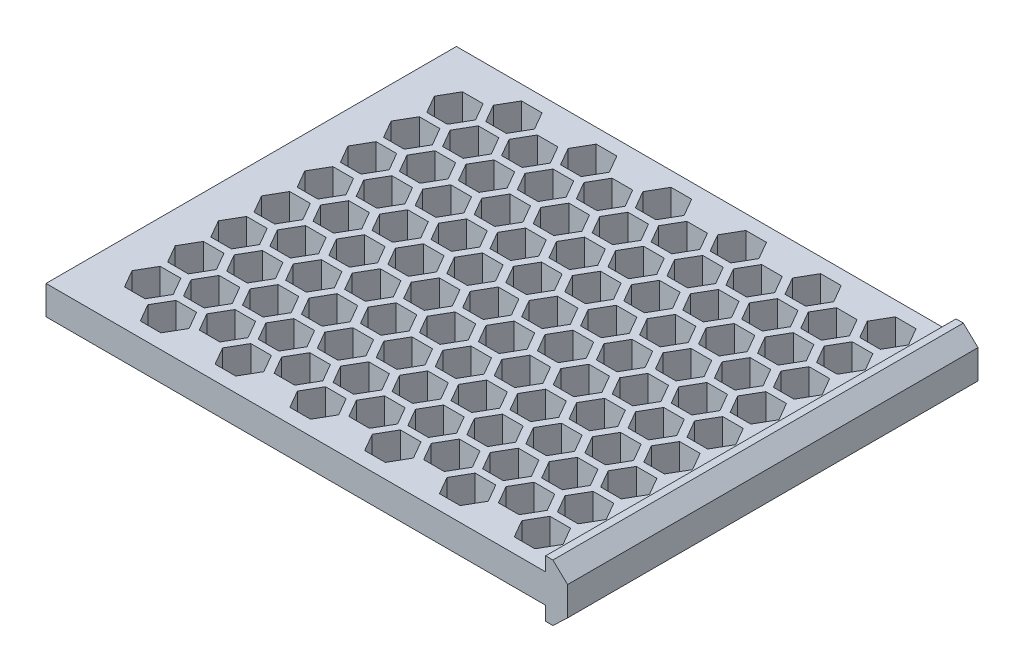
SolidWorks part; units mm, degrees
ref_plane "Front Plane" through (0, 0, 0) normal (0, 0, 1) x (1, 0, 0)
ref_plane "Top Plane" through (0, 0, 0) normal (0, 1, 0) x (1, 0, 0)
ref_plane "Right Plane" through (0, 0, 0) normal (1, 0, 0) x (0, 0, -1)
sketch "Sketch1" plane through (0, 0, 0) normal (0, 0, 1) x (1, 0, 0)
  line L0 (0, 4.05) -> (-140, 4.05)
  line L1 (0, -4.05) -> (-140, -4.05)
  line L2 (-140, -4.05) -> (-140, 4.05)
  line B0 (0, 7.95) -> (2.04, 7.95)
  line B1 (6.1524, 4.048) -> (6.1524, -4.048)
  line B2 (2.04, -7.95) -> (0, -7.95)
  line B3 (0, -7.95) -> (0, 7.95)
  line B4 (2.04, 7.95) -> (6.1524, 4.048)
  line B5 (6.1524, -4.048) -> (2.04, -7.95)
  line B6 (0, 4.05) -> (0, -4.05) construction
  dimension "D1" = 140
sketch_block_instance "Extrusion Profile-2"
sketch_block "Extrusion Profile" parameters "D1"=8.44, "D2"=2.6, "D3"=6, "D4"=16.7, "D6"=5.6686, "D7"=2.0404, "D8"=8.0963, "D9"=15.9, "D5"=2.4157
extrude "Boss-Extrude1" add sketch "Sketch1" along normal blind 115 contours L1 B3 L0 L2 | B2 B5 B1 B4 B0 B3 region at (-70, 0, 0) region at (2.7416, 0, 0)
sketch "Sketch2" plane through (0, 4.05, 0) normal (0, 1, 0) x (1, 0, 0)
  line L0 (-16.1488, -12.65) -> (-14.3301, -11.6) construction
  line L1 (-4.2265, -9.1) -> (-7.1132, -4.1)
  line L2 (-7.1132, -4.1) -> (-12.8868, -4.1)
  line L3 (-12.8868, -4.1) -> (-15.7735, -9.1)
  line L4 (-15.7735, -9.1) -> (-12.8868, -14.1)
  line L5 (-12.8868, -14.1) -> (-7.1132, -14.1)
  line L6 (-7.1132, -14.1) -> (-4.2265, -9.1)
  line L7 (0, -115) -> (0, 0) construction
  line L8 (-4.2265, -21.2) -> (-7.1132, -16.2)
  line L9 (-7.1132, -16.2) -> (-12.8868, -16.2)
  line L10 (-12.8868, -16.2) -> (-15.7735, -21.2)
  line L11 (-15.7735, -21.2) -> (-12.8868, -26.2)
  line L12 (-12.8868, -26.2) -> (-7.1132, -26.2)
  line L13 (-7.1132, -26.2) -> (-4.2265, -21.2)
  line L14 (-4.2265, -33.3) -> (-7.1132, -28.3)
  line L15 (-7.1132, -28.3) -> (-12.8868, -28.3)
  line L16 (-12.8868, -28.3) -> (-15.7735, -33.3)
  line L17 (-15.7735, -33.3) -> (-12.8868, -38.3)
  line L18 (-12.8868, -38.3) -> (-7.1132, -38.3)
  line L19 (-7.1132, -38.3) -> (-4.2265, -33.3)
  line L20 (-4.2265, -45.4) -> (-7.1132, -40.4)
  line L21 (-7.1132, -40.4) -> (-12.8868, -40.4)
  line L22 (-12.8868, -40.4) -> (-15.7735, -45.4)
  line L23 (-15.7735, -45.4) -> (-12.8868, -50.4)
  line L24 (-12.8868, -50.4) -> (-7.1132, -50.4)
  line L25 (-7.1132, -50.4) -> (-4.2265, -45.4)
  line L26 (-4.2265, -57.5) -> (-7.1132, -52.5)
  line L27 (-7.1132, -52.5) -> (-12.8868, -52.5)
  line L28 (-12.8868, -52.5) -> (-15.7735, -57.5)
  line L29 (-15.7735, -57.5) -> (-12.8868, -62.5)
  line L30 (-12.8868, -62.5) -> (-7.1132, -62.5)
  line L31 (-7.1132, -62.5) -> (-4.2265, -57.5)
  line L32 (-4.2265, -69.6) -> (-7.1132, -64.6)
  line L33 (-7.1132, -64.6) -> (-12.8868, -64.6)
  line L34 (-12.8868, -64.6) -> (-15.7735, -69.6)
  line L35 (-15.7735, -69.6) -> (-12.8868, -74.6)
  line L36 (-12.8868, -74.6) -> (-7.1132, -74.6)
  line L37 (-7.1132, -74.6) -> (-4.2265, -69.6)
  line L38 (-4.2265, -81.7) -> (-7.1132, -76.7)
  line L39 (-7.1132, -76.7) -> (-12.8868, -76.7)
  line L40 (-12.8868, -76.7) -> (-15.7735, -81.7)
  line L41 (-15.7735, -81.7) -> (-12.8868, -86.7)
  line L42 (-12.8868, -86.7) -> (-7.1132, -86.7)
  line L43 (-7.1132, -86.7) -> (-4.2265, -81.7)
  line L44 (-4.2265, -93.8) -> (-7.1132, -88.8)
  line L45 (-7.1132, -88.8) -> (-12.8868, -88.8)
  line L46 (-12.8868, -88.8) -> (-15.7735, -93.8)
  line L47 (-15.7735, -93.8) -> (-12.8868, -98.8)
  line L48 (-12.8868, -98.8) -> (-7.1132, -98.8)
  line L49 (-7.1132, -98.8) -> (-4.2265, -93.8)
  line L50 (-4.2265, -105.9) -> (-7.1132, -100.9)
  line L51 (-7.1132, -100.9) -> (-12.8868, -100.9)
  line L52 (-12.8868, -100.9) -> (-15.7735, -105.9)
  line L53 (-15.7735, -105.9) -> (-12.8868, -110.9)
  line L54 (-12.8868, -110.9) -> (-7.1132, -110.9)
  line L55 (-7.1132, -110.9) -> (-4.2265, -105.9)
  line L56 (-14.7054, -15.15) -> (-17.5922, -10.15)
  line L57 (-17.5922, -10.15) -> (-23.3657, -10.15)
  line L58 (-23.3657, -10.15) -> (-26.2524, -15.15)
  line L59 (-10, -4.1) -> (-10, 0) construction
  line L60 (0, 0) -> (-140, 0) construction
  line L61 (-10, -110.9) -> (-10, -115) construction
  line L62 (-26.2524, -15.15) -> (-23.3657, -20.15)
  line L69 (-4.2265, -118) -> (-7.1132, -113) [skipped]
  line L70 (-7.1132, -113) -> (-12.8868, -113) [skipped]
  line L71 (-12.8868, -113) -> (-15.7735, -118) [skipped]
  line L72 (-15.7735, -118) -> (-12.8868, -123) [skipped]
  line L73 (-12.8868, -123) -> (-7.1132, -123) [skipped]
  line L74 (-7.1132, -123) -> (-4.2265, -118) [skipped]
  line L75 (0, -115) -> (-140, -115) construction
  line L76 (-23.3657, -20.15) -> (-17.5922, -20.15)
  line L77 (-17.5922, -20.15) -> (-14.7054, -15.15)
  line L79 (-16.1488, -17.65) -> (-14.3301, -18.7) construction
  line L81 (-10, -14.1) -> (-10, -16.2) construction
  line L83 (-14.7054, -27.25) -> (-17.5922, -22.25)
  line L84 (-17.5922, -22.25) -> (-23.3657, -22.25)
  line L85 (-23.3657, -22.25) -> (-26.2524, -27.25)
  line L86 (-26.2524, -27.25) -> (-23.3657, -32.25)
  line L87 (-23.3657, -32.25) -> (-17.5922, -32.25)
  line L88 (-17.5922, -32.25) -> (-14.7054, -27.25)
  line L89 (-14.7054, -39.35) -> (-17.5922, -34.35)
  line L90 (-17.5922, -34.35) -> (-23.3657, -34.35)
  line L91 (-23.3657, -34.35) -> (-26.2524, -39.35)
  line L92 (-26.2524, -39.35) -> (-23.3657, -44.35)
  line L93 (-23.3657, -44.35) -> (-17.5922, -44.35)
  line L94 (-17.5922, -44.35) -> (-14.7054, -39.35)
  line L95 (-14.7054, -51.45) -> (-17.5922, -46.45)
  line L96 (-17.5922, -46.45) -> (-23.3657, -46.45)
  line L97 (-23.3657, -46.45) -> (-26.2524, -51.45)
  line L98 (-26.2524, -51.45) -> (-23.3657, -56.45)
  line L99 (-23.3657, -56.45) -> (-17.5922, -56.45)
  line L100 (-17.5922, -56.45) -> (-14.7054, -51.45)
  line L101 (-14.7054, -63.55) -> (-17.5922, -58.55)
  line L102 (-17.5922, -58.55) -> (-23.3657, -58.55)
  line L103 (-23.3657, -58.55) -> (-26.2524, -63.55)
  line L104 (-26.2524, -63.55) -> (-23.3657, -68.55)
  line L105 (-23.3657, -68.55) -> (-17.5922, -68.55)
  line L106 (-17.5922, -68.55) -> (-14.7054, -63.55)
  line L107 (-14.7054, -75.65) -> (-17.5922, -70.65)
  line L108 (-17.5922, -70.65) -> (-23.3657, -70.65)
  line L109 (-23.3657, -70.65) -> (-26.2524, -75.65)
  line L110 (-26.2524, -75.65) -> (-23.3657, -80.65)
  line L111 (-23.3657, -80.65) -> (-17.5922, -80.65)
  line L112 (-17.5922, -80.65) -> (-14.7054, -75.65)
  line L113 (-14.7054, -87.75) -> (-17.5922, -82.75)
  line L114 (-17.5922, -82.75) -> (-23.3657, -82.75)
  line L115 (-23.3657, -82.75) -> (-26.2524, -87.75)
  line L116 (-26.2524, -87.75) -> (-23.3657, -92.75)
  line L117 (-23.3657, -92.75) -> (-17.5922, -92.75)
  line L118 (-17.5922, -92.75) -> (-14.7054, -87.75)
  line L119 (-14.7054, -99.85) -> (-17.5922, -94.85)
  line L120 (-17.5922, -94.85) -> (-23.3657, -94.85)
  line L121 (-23.3657, -94.85) -> (-26.2524, -99.85)
  line L122 (-26.2524, -99.85) -> (-23.3657, -104.85)
  line L123 (-23.3657, -104.85) -> (-17.5922, -104.85)
  line L124 (-17.5922, -104.85) -> (-14.7054, -99.85)
  line L125 (-14.7054, -15.15) -> (-14.7054, -27.25) construction
  line L126 (-25.1843, -9.1) -> (-28.0711, -4.1)
  line L127 (-28.0711, -4.1) -> (-33.8446, -4.1)
  line L128 (-33.8446, -4.1) -> (-36.7313, -9.1)
  line L129 (-36.7313, -9.1) -> (-33.8446, -14.1)
  line L130 (-33.8446, -14.1) -> (-28.0711, -14.1)
  line L131 (-28.0711, -14.1) -> (-25.1843, -9.1)
  line L132 (-25.1843, -21.2) -> (-28.0711, -16.2)
  line L133 (-28.0711, -16.2) -> (-33.8446, -16.2)
  line L134 (-33.8446, -16.2) -> (-36.7313, -21.2)
  line L135 (-36.7313, -21.2) -> (-33.8446, -26.2)
  line L136 (-33.8446, -26.2) -> (-28.0711, -26.2)
  line L137 (-28.0711, -26.2) -> (-25.1843, -21.2)
  line L138 (-25.1843, -33.3) -> (-28.0711, -28.3)
  line L139 (-28.0711, -28.3) -> (-33.8446, -28.3)
  line L140 (-33.8446, -28.3) -> (-36.7313, -33.3)
  line L141 (-36.7313, -33.3) -> (-33.8446, -38.3)
  line L142 (-33.8446, -38.3) -> (-28.0711, -38.3)
  line L143 (-28.0711, -38.3) -> (-25.1843, -33.3)
  line L144 (-25.1843, -45.4) -> (-28.0711, -40.4)
  line L145 (-28.0711, -40.4) -> (-33.8446, -40.4)
  line L146 (-33.8446, -40.4) -> (-36.7313, -45.4)
  line L147 (-36.7313, -45.4) -> (-33.8446, -50.4)
  line L148 (-33.8446, -50.4) -> (-28.0711, -50.4)
  line L149 (-28.0711, -50.4) -> (-25.1843, -45.4)
  line L150 (-25.1843, -57.5) -> (-28.0711, -52.5)
  line L151 (-28.0711, -52.5) -> (-33.8446, -52.5)
  line L152 (-33.8446, -52.5) -> (-36.7313, -57.5)
  line L153 (-36.7313, -57.5) -> (-33.8446, -62.5)
  line L154 (-33.8446, -62.5) -> (-28.0711, -62.5)
  line L155 (-28.0711, -62.5) -> (-25.1843, -57.5)
  line L156 (-25.1843, -69.6) -> (-28.0711, -64.6)
  line L157 (-28.0711, -64.6) -> (-33.8446, -64.6)
  line L158 (-33.8446, -64.6) -> (-36.7313, -69.6)
  line L159 (-36.7313, -69.6) -> (-33.8446, -74.6)
  line L160 (-33.8446, -74.6) -> (-28.0711, -74.6)
  line L161 (-28.0711, -74.6) -> (-25.1843, -69.6)
  line L162 (-25.1843, -81.7) -> (-28.0711, -76.7)
  line L163 (-28.0711, -76.7) -> (-33.8446, -76.7)
  line L164 (-33.8446, -76.7) -> (-36.7313, -81.7)
  line L165 (-36.7313, -81.7) -> (-33.8446, -86.7)
  line L166 (-33.8446, -86.7) -> (-28.0711, -86.7)
  line L167 (-28.0711, -86.7) -> (-25.1843, -81.7)
  line L168 (-25.1843, -93.8) -> (-28.0711, -88.8)
  line L169 (-28.0711, -88.8) -> (-33.8446, -88.8)
  line L170 (-33.8446, -88.8) -> (-36.7313, -93.8)
  line L171 (-36.7313, -93.8) -> (-33.8446, -98.8)
  line L172 (-33.8446, -98.8) -> (-28.0711, -98.8)
  line L173 (-28.0711, -98.8) -> (-25.1843, -93.8)
  line L174 (-25.1843, -105.9) -> (-28.0711, -100.9)
  line L175 (-28.0711, -100.9) -> (-33.8446, -100.9)
  line L176 (-33.8446, -100.9) -> (-36.7313, -105.9)
  line L177 (-36.7313, -105.9) -> (-33.8446, -110.9)
  line L178 (-33.8446, -110.9) -> (-28.0711, -110.9)
  line L179 (-28.0711, -110.9) -> (-25.1843, -105.9)
  line L180 (-35.6632, -15.15) -> (-38.55, -10.15)
  line L181 (-38.55, -10.15) -> (-44.3235, -10.15)
  line L182 (-44.3235, -10.15) -> (-47.2102, -15.15)
  line L183 (-47.2102, -15.15) -> (-44.3235, -20.15)
  line L184 (-44.3235, -20.15) -> (-38.55, -20.15)
  line L185 (-38.55, -20.15) -> (-35.6632, -15.15)
  line L186 (-35.6632, -27.25) -> (-38.55, -22.25)
  line L187 (-38.55, -22.25) -> (-44.3235, -22.25)
  line L188 (-44.3235, -22.25) -> (-47.2102, -27.25)
  line L189 (-47.2102, -27.25) -> (-44.3235, -32.25)
  line L190 (-44.3235, -32.25) -> (-38.55, -32.25)
  line L191 (-38.55, -32.25) -> (-35.6632, -27.25)
  line L192 (-35.6632, -39.35) -> (-38.55, -34.35)
  line L193 (-38.55, -34.35) -> (-44.3235, -34.35)
  line L194 (-44.3235, -34.35) -> (-47.2102, -39.35)
  line L195 (-47.2102, -39.35) -> (-44.3235, -44.35)
  line L196 (-44.3235, -44.35) -> (-38.55, -44.35)
  line L197 (-38.55, -44.35) -> (-35.6632, -39.35)
  line L198 (-35.6632, -51.45) -> (-38.55, -46.45)
  line L199 (-38.55, -46.45) -> (-44.3235, -46.45)
  line L200 (-44.3235, -46.45) -> (-47.2102, -51.45)
  line L201 (-47.2102, -51.45) -> (-44.3235, -56.45)
  line L202 (-44.3235, -56.45) -> (-38.55, -56.45)
  line L203 (-38.55, -56.45) -> (-35.6632, -51.45)
  line L204 (-35.6632, -63.55) -> (-38.55, -58.55)
  line L205 (-38.55, -58.55) -> (-44.3235, -58.55)
  line L206 (-44.3235, -58.55) -> (-47.2102, -63.55)
  line L207 (-47.2102, -63.55) -> (-44.3235, -68.55)
  line L208 (-44.3235, -68.55) -> (-38.55, -68.55)
  line L209 (-38.55, -68.55) -> (-35.6632, -63.55)
  line L210 (-35.6632, -75.65) -> (-38.55, -70.65)
  line L211 (-38.55, -70.65) -> (-44.3235, -70.65)
  line L212 (-44.3235, -70.65) -> (-47.2102, -75.65)
  line L213 (-47.2102, -75.65) -> (-44.3235, -80.65)
  line L214 (-44.3235, -80.65) -> (-38.55, -80.65)
  line L215 (-38.55, -80.65) -> (-35.6632, -75.65)
  line L216 (-35.6632, -87.75) -> (-38.55, -82.75)
  line L217 (-38.55, -82.75) -> (-44.3235, -82.75)
  line L218 (-44.3235, -82.75) -> (-47.2102, -87.75)
  line L219 (-47.2102, -87.75) -> (-44.3235, -92.75)
  line L220 (-44.3235, -92.75) -> (-38.55, -92.75)
  line L221 (-38.55, -92.75) -> (-35.6632, -87.75)
  line L222 (-35.6632, -99.85) -> (-38.55, -94.85)
  line L223 (-38.55, -94.85) -> (-44.3235, -94.85)
  line L224 (-44.3235, -94.85) -> (-47.2102, -99.85)
  line L225 (-47.2102, -99.85) -> (-44.3235, -104.85)
  line L226 (-44.3235, -104.85) -> (-38.55, -104.85)
  line L227 (-38.55, -104.85) -> (-35.6632, -99.85)
  line L228 (-37.1066, -12.65) -> (-35.2879, -11.6) construction
  line L229 (-30.9578, -4.1) -> (-30.9578, 0) construction
  line L230 (-30.9578, -110.9) -> (-30.9578, -115) construction
  line L231 (-37.1066, -17.65) -> (-35.2879, -18.7) construction
  line L232 (-30.9578, -15.15) -> (-30.9578, -14.1)
  line L233 (-35.6632, -15.15) -> (-35.6632, -27.25) construction
  line L234 (-46.1421, -9.1) -> (-49.0289, -4.1)
  line L235 (-49.0289, -4.1) -> (-54.8024, -4.1)
  line L236 (-54.8024, -4.1) -> (-57.6891, -9.1)
  line L237 (-57.6891, -9.1) -> (-54.8024, -14.1)
  line L238 (-54.8024, -14.1) -> (-49.0289, -14.1)
  line L239 (-49.0289, -14.1) -> (-46.1421, -9.1)
  line L240 (-46.1421, -21.2) -> (-49.0289, -16.2)
  line L241 (-49.0289, -16.2) -> (-54.8024, -16.2)
  line L242 (-54.8024, -16.2) -> (-57.6891, -21.2)
  line L243 (-57.6891, -21.2) -> (-54.8024, -26.2)
  line L244 (-54.8024, -26.2) -> (-49.0289, -26.2)
  line L245 (-49.0289, -26.2) -> (-46.1421, -21.2)
  line L246 (-46.1421, -33.3) -> (-49.0289, -28.3)
  line L247 (-49.0289, -28.3) -> (-54.8024, -28.3)
  line L248 (-54.8024, -28.3) -> (-57.6891, -33.3)
  line L249 (-57.6891, -33.3) -> (-54.8024, -38.3)
  line L250 (-54.8024, -38.3) -> (-49.0289, -38.3)
  line L251 (-49.0289, -38.3) -> (-46.1421, -33.3)
  line L252 (-46.1421, -45.4) -> (-49.0289, -40.4)
  line L253 (-49.0289, -40.4) -> (-54.8024, -40.4)
  line L254 (-54.8024, -40.4) -> (-57.6891, -45.4)
  line L255 (-57.6891, -45.4) -> (-54.8024, -50.4)
  line L256 (-54.8024, -50.4) -> (-49.0289, -50.4)
  line L257 (-49.0289, -50.4) -> (-46.1421, -45.4)
  line L258 (-46.1421, -57.5) -> (-49.0289, -52.5)
  line L259 (-49.0289, -52.5) -> (-54.8024, -52.5)
  line L260 (-54.8024, -52.5) -> (-57.6891, -57.5)
  line L261 (-57.6891, -57.5) -> (-54.8024, -62.5)
  line L262 (-54.8024, -62.5) -> (-49.0289, -62.5)
  line L263 (-49.0289, -62.5) -> (-46.1421, -57.5)
  line L264 (-46.1421, -69.6) -> (-49.0289, -64.6)
  line L265 (-49.0289, -64.6) -> (-54.8024, -64.6)
  line L266 (-54.8024, -64.6) -> (-57.6891, -69.6)
  line L267 (-57.6891, -69.6) -> (-54.8024, -74.6)
  line L268 (-54.8024, -74.6) -> (-49.0289, -74.6)
  line L269 (-49.0289, -74.6) -> (-46.1421, -69.6)
  line L270 (-46.1421, -81.7) -> (-49.0289, -76.7)
  line L271 (-49.0289, -76.7) -> (-54.8024, -76.7)
  line L272 (-54.8024, -76.7) -> (-57.6891, -81.7)
  line L273 (-57.6891, -81.7) -> (-54.8024, -86.7)
  line L274 (-54.8024, -86.7) -> (-49.0289, -86.7)
  line L275 (-49.0289, -86.7) -> (-46.1421, -81.7)
  line L276 (-46.1421, -93.8) -> (-49.0289, -88.8)
  line L277 (-49.0289, -88.8) -> (-54.8024, -88.8)
  line L278 (-54.8024, -88.8) -> (-57.6891, -93.8)
  line L279 (-57.6891, -93.8) -> (-54.8024, -98.8)
  line L280 (-54.8024, -98.8) -> (-49.0289, -98.8)
  line L281 (-49.0289, -98.8) -> (-46.1421, -93.8)
  line L282 (-46.1421, -105.9) -> (-49.0289, -100.9)
  line L283 (-49.0289, -100.9) -> (-54.8024, -100.9)
  line L284 (-54.8024, -100.9) -> (-57.6891, -105.9)
  line L285 (-57.6891, -105.9) -> (-54.8024, -110.9)
  line L286 (-54.8024, -110.9) -> (-49.0289, -110.9)
  line L287 (-49.0289, -110.9) -> (-46.1421, -105.9)
  line L288 (-56.621, -15.15) -> (-59.5078, -10.15)
  line L289 (-59.5078, -10.15) -> (-65.2813, -10.15)
  line L290 (-65.2813, -10.15) -> (-68.168, -15.15)
  line L291 (-68.168, -15.15) -> (-65.2813, -20.15)
  line L292 (-65.2813, -20.15) -> (-59.5078, -20.15)
  line L293 (-59.5078, -20.15) -> (-56.621, -15.15)
  line L294 (-56.621, -27.25) -> (-59.5078, -22.25)
  line L295 (-59.5078, -22.25) -> (-65.2813, -22.25)
  line L296 (-65.2813, -22.25) -> (-68.168, -27.25)
  line L297 (-68.168, -27.25) -> (-65.2813, -32.25)
  line L298 (-65.2813, -32.25) -> (-59.5078, -32.25)
  line L299 (-59.5078, -32.25) -> (-56.621, -27.25)
  line L300 (-56.621, -39.35) -> (-59.5078, -34.35)
  line L301 (-59.5078, -34.35) -> (-65.2813, -34.35)
  line L302 (-65.2813, -34.35) -> (-68.168, -39.35)
  line L303 (-68.168, -39.35) -> (-65.2813, -44.35)
  line L304 (-65.2813, -44.35) -> (-59.5078, -44.35)
  line L305 (-59.5078, -44.35) -> (-56.621, -39.35)
  line L306 (-56.621, -51.45) -> (-59.5078, -46.45)
  line L307 (-59.5078, -46.45) -> (-65.2813, -46.45)
  line L308 (-65.2813, -46.45) -> (-68.168, -51.45)
  line L309 (-68.168, -51.45) -> (-65.2813, -56.45)
  line L310 (-65.2813, -56.45) -> (-59.5078, -56.45)
  line L311 (-59.5078, -56.45) -> (-56.621, -51.45)
  line L312 (-56.621, -63.55) -> (-59.5078, -58.55)
  line L313 (-59.5078, -58.55) -> (-65.2813, -58.55)
  line L314 (-65.2813, -58.55) -> (-68.168, -63.55)
  line L315 (-68.168, -63.55) -> (-65.2813, -68.55)
  line L316 (-65.2813, -68.55) -> (-59.5078, -68.55)
  line L317 (-59.5078, -68.55) -> (-56.621, -63.55)
  line L318 (-56.621, -75.65) -> (-59.5078, -70.65)
  line L319 (-59.5078, -70.65) -> (-65.2813, -70.65)
  line L320 (-65.2813, -70.65) -> (-68.168, -75.65)
  line L321 (-68.168, -75.65) -> (-65.2813, -80.65)
  line L322 (-65.2813, -80.65) -> (-59.5078, -80.65)
  line L323 (-59.5078, -80.65) -> (-56.621, -75.65)
  line L324 (-56.621, -87.75) -> (-59.5078, -82.75)
  line L325 (-59.5078, -82.75) -> (-65.2813, -82.75)
  line L326 (-65.2813, -82.75) -> (-68.168, -87.75)
  line L327 (-68.168, -87.75) -> (-65.2813, -92.75)
  line L328 (-65.2813, -92.75) -> (-59.5078, -92.75)
  line L329 (-59.5078, -92.75) -> (-56.621, -87.75)
  line L330 (-56.621, -99.85) -> (-59.5078, -94.85)
  line L331 (-59.5078, -94.85) -> (-65.2813, -94.85)
  line L332 (-65.2813, -94.85) -> (-68.168, -99.85)
  line L333 (-68.168, -99.85) -> (-65.2813, -104.85)
  line L334 (-65.2813, -104.85) -> (-59.5078, -104.85)
  line L335 (-59.5078, -104.85) -> (-56.621, -99.85)
  line L336 (-58.0644, -12.65) -> (-56.2458, -11.6) construction
  line L337 (-51.9156, -4.1) -> (-51.9156, 0) construction
  line L338 (-51.9156, -110.9) -> (-51.9156, -115) construction
  line L339 (-58.0644, -17.65) -> (-56.2458, -18.7) construction
  line L340 (-51.9156, -14.1) -> (-51.9156, -16.2) construction
  line L341 (-56.621, -15.15) -> (-56.621, -27.25) construction
  line L342 (-67.0999, -9.1) -> (-69.9867, -4.1)
  line L343 (-69.9867, -4.1) -> (-75.7602, -4.1)
  line L344 (-75.7602, -4.1) -> (-78.6469, -9.1)
  line L345 (-78.6469, -9.1) -> (-75.7602, -14.1)
  line L346 (-75.7602, -14.1) -> (-69.9867, -14.1)
  line L347 (-69.9867, -14.1) -> (-67.0999, -9.1)
  line L348 (-67.0999, -21.2) -> (-69.9867, -16.2)
  line L349 (-69.9867, -16.2) -> (-75.7602, -16.2)
  line L350 (-75.7602, -16.2) -> (-78.6469, -21.2)
  line L351 (-78.6469, -21.2) -> (-75.7602, -26.2)
  line L352 (-75.7602, -26.2) -> (-69.9867, -26.2)
  line L353 (-69.9867, -26.2) -> (-67.0999, -21.2)
  line L354 (-67.0999, -33.3) -> (-69.9867, -28.3)
  line L355 (-69.9867, -28.3) -> (-75.7602, -28.3)
  line L356 (-75.7602, -28.3) -> (-78.6469, -33.3)
  line L357 (-78.6469, -33.3) -> (-75.7602, -38.3)
  line L358 (-75.7602, -38.3) -> (-69.9867, -38.3)
  line L359 (-69.9867, -38.3) -> (-67.0999, -33.3)
  line L360 (-67.0999, -45.4) -> (-69.9867, -40.4)
  line L361 (-69.9867, -40.4) -> (-75.7602, -40.4)
  line L362 (-75.7602, -40.4) -> (-78.6469, -45.4)
  line L363 (-78.6469, -45.4) -> (-75.7602, -50.4)
  line L364 (-75.7602, -50.4) -> (-69.9867, -50.4)
  line L365 (-69.9867, -50.4) -> (-67.0999, -45.4)
  line L366 (-67.0999, -57.5) -> (-69.9867, -52.5)
  line L367 (-69.9867, -52.5) -> (-75.7602, -52.5)
  line L368 (-75.7602, -52.5) -> (-78.6469, -57.5)
  line L369 (-78.6469, -57.5) -> (-75.7602, -62.5)
  line L370 (-75.7602, -62.5) -> (-69.9867, -62.5)
  line L371 (-69.9867, -62.5) -> (-67.0999, -57.5)
  line L372 (-67.0999, -69.6) -> (-69.9867, -64.6)
  line L373 (-69.9867, -64.6) -> (-75.7602, -64.6)
  line L374 (-75.7602, -64.6) -> (-78.6469, -69.6)
  line L375 (-78.6469, -69.6) -> (-75.7602, -74.6)
  line L376 (-75.7602, -74.6) -> (-69.9867, -74.6)
  line L377 (-69.9867, -74.6) -> (-67.0999, -69.6)
  line L378 (-67.0999, -81.7) -> (-69.9867, -76.7)
  line L379 (-69.9867, -76.7) -> (-75.7602, -76.7)
  line L380 (-75.7602, -76.7) -> (-78.6469, -81.7)
  line L381 (-78.6469, -81.7) -> (-75.7602, -86.7)
  line L382 (-75.7602, -86.7) -> (-69.9867, -86.7)
  line L383 (-69.9867, -86.7) -> (-67.0999, -81.7)
  line L384 (-67.0999, -93.8) -> (-69.9867, -88.8)
  line L385 (-69.9867, -88.8) -> (-75.7602, -88.8)
  line L386 (-75.7602, -88.8) -> (-78.6469, -93.8)
  line L387 (-78.6469, -93.8) -> (-75.7602, -98.8)
  line L388 (-75.7602, -98.8) -> (-69.9867, -98.8)
  line L389 (-69.9867, -98.8) -> (-67.0999, -93.8)
  line L390 (-67.0999, -105.9) -> (-69.9867, -100.9)
  line L391 (-69.9867, -100.9) -> (-75.7602, -100.9)
  line L392 (-75.7602, -100.9) -> (-78.6469, -105.9)
  line L393 (-78.6469, -105.9) -> (-75.7602, -110.9)
  line L394 (-75.7602, -110.9) -> (-69.9867, -110.9)
  line L395 (-69.9867, -110.9) -> (-67.0999, -105.9)
  line L396 (-77.5788, -15.15) -> (-80.4656, -10.15)
  line L397 (-80.4656, -10.15) -> (-86.2391, -10.15)
  line L398 (-86.2391, -10.15) -> (-89.1259, -15.15)
  line L399 (-89.1259, -15.15) -> (-86.2391, -20.15)
  line L400 (-86.2391, -20.15) -> (-80.4656, -20.15)
  line L401 (-80.4656, -20.15) -> (-77.5788, -15.15)
  line L402 (-77.5788, -27.25) -> (-80.4656, -22.25)
  line L403 (-80.4656, -22.25) -> (-86.2391, -22.25)
  line L404 (-86.2391, -22.25) -> (-89.1259, -27.25)
  line L405 (-89.1259, -27.25) -> (-86.2391, -32.25)
  line L406 (-86.2391, -32.25) -> (-80.4656, -32.25)
  line L407 (-80.4656, -32.25) -> (-77.5788, -27.25)
  line L408 (-77.5788, -39.35) -> (-80.4656, -34.35)
  line L409 (-80.4656, -34.35) -> (-86.2391, -34.35)
  line L410 (-86.2391, -34.35) -> (-89.1259, -39.35)
  line L411 (-89.1259, -39.35) -> (-86.2391, -44.35)
  line L412 (-86.2391, -44.35) -> (-80.4656, -44.35)
  line L413 (-80.4656, -44.35) -> (-77.5788, -39.35)
  line L414 (-77.5788, -51.45) -> (-80.4656, -46.45)
  line L415 (-80.4656, -46.45) -> (-86.2391, -46.45)
  line L416 (-86.2391, -46.45) -> (-89.1259, -51.45)
  line L417 (-89.1259, -51.45) -> (-86.2391, -56.45)
  line L418 (-86.2391, -56.45) -> (-80.4656, -56.45)
  line L419 (-80.4656, -56.45) -> (-77.5788, -51.45)
  line L420 (-77.5788, -63.55) -> (-80.4656, -58.55)
  line L421 (-80.4656, -58.55) -> (-86.2391, -58.55)
  line L422 (-86.2391, -58.55) -> (-89.1259, -63.55)
  line L423 (-89.1259, -63.55) -> (-86.2391, -68.55)
  line L424 (-86.2391, -68.55) -> (-80.4656, -68.55)
  line L425 (-80.4656, -68.55) -> (-77.5788, -63.55)
  line L426 (-77.5788, -75.65) -> (-80.4656, -70.65)
  line L427 (-80.4656, -70.65) -> (-86.2391, -70.65)
  line L428 (-86.2391, -70.65) -> (-89.1259, -75.65)
  line L429 (-89.1259, -75.65) -> (-86.2391, -80.65)
  line L430 (-86.2391, -80.65) -> (-80.4656, -80.65)
  line L431 (-80.4656, -80.65) -> (-77.5788, -75.65)
  line L432 (-77.5788, -87.75) -> (-80.4656, -82.75)
  line L433 (-80.4656, -82.75) -> (-86.2391, -82.75)
  line L434 (-86.2391, -82.75) -> (-89.1259, -87.75)
  line L435 (-89.1259, -87.75) -> (-86.2391, -92.75)
  line L436 (-86.2391, -92.75) -> (-80.4656, -92.75)
  line L437 (-80.4656, -92.75) -> (-77.5788, -87.75)
  line L438 (-77.5788, -99.85) -> (-80.4656, -94.85)
  line L439 (-80.4656, -94.85) -> (-86.2391, -94.85)
  line L440 (-86.2391, -94.85) -> (-89.1259, -99.85)
  line L441 (-89.1259, -99.85) -> (-86.2391, -104.85)
  line L442 (-86.2391, -104.85) -> (-80.4656, -104.85)
  line L443 (-80.4656, -104.85) -> (-77.5788, -99.85)
  line L444 (-79.0222, -12.65) -> (-77.2036, -11.6) construction
  line L445 (-72.8734, -4.1) -> (-72.8734, 0) construction
  line L446 (-72.8734, -110.9) -> (-72.8734, -115) construction
  line L447 (-79.0222, -17.65) -> (-77.2036, -18.7) construction
  line L448 (-72.8734, -14.1) -> (-72.8734, -16.2) construction
  line L449 (-77.5788, -15.15) -> (-77.5788, -27.25) construction
  line L450 (-88.0578, -9.1) -> (-90.9445, -4.1)
  line L451 (-90.9445, -4.1) -> (-96.718, -4.1)
  line L452 (-96.718, -4.1) -> (-99.6048, -9.1)
  line L453 (-99.6048, -9.1) -> (-96.718, -14.1)
  line L454 (-96.718, -14.1) -> (-90.9445, -14.1)
  line L455 (-90.9445, -14.1) -> (-88.0578, -9.1)
  line L456 (-88.0578, -21.2) -> (-90.9445, -16.2)
  line L457 (-90.9445, -16.2) -> (-96.718, -16.2)
  line L458 (-96.718, -16.2) -> (-99.6048, -21.2)
  line L459 (-99.6048, -21.2) -> (-96.718, -26.2)
  line L460 (-96.718, -26.2) -> (-90.9445, -26.2)
  line L461 (-90.9445, -26.2) -> (-88.0578, -21.2)
  line L462 (-88.0578, -33.3) -> (-90.9445, -28.3)
  line L463 (-90.9445, -28.3) -> (-96.718, -28.3)
  line L464 (-96.718, -28.3) -> (-99.6048, -33.3)
  line L465 (-99.6048, -33.3) -> (-96.718, -38.3)
  line L466 (-96.718, -38.3) -> (-90.9445, -38.3)
  line L467 (-90.9445, -38.3) -> (-88.0578, -33.3)
  line L468 (-88.0578, -45.4) -> (-90.9445, -40.4)
  line L469 (-90.9445, -40.4) -> (-96.718, -40.4)
  line L470 (-96.718, -40.4) -> (-99.6048, -45.4)
  line L471 (-99.6048, -45.4) -> (-96.718, -50.4)
  line L472 (-96.718, -50.4) -> (-90.9445, -50.4)
  line L473 (-90.9445, -50.4) -> (-88.0578, -45.4)
  line L474 (-88.0578, -57.5) -> (-90.9445, -52.5)
  line L475 (-90.9445, -52.5) -> (-96.718, -52.5)
  line L476 (-96.718, -52.5) -> (-99.6048, -57.5)
  line L477 (-99.6048, -57.5) -> (-96.718, -62.5)
  line L478 (-96.718, -62.5) -> (-90.9445, -62.5)
  line L479 (-90.9445, -62.5) -> (-88.0578, -57.5)
  line L480 (-88.0578, -69.6) -> (-90.9445, -64.6)
  line L481 (-90.9445, -64.6) -> (-96.718, -64.6)
  line L482 (-96.718, -64.6) -> (-99.6048, -69.6)
  line L483 (-99.6048, -69.6) -> (-96.718, -74.6)
  line L484 (-96.718, -74.6) -> (-90.9445, -74.6)
  line L485 (-90.9445, -74.6) -> (-88.0578, -69.6)
  line L486 (-88.0578, -81.7) -> (-90.9445, -76.7)
  line L487 (-90.9445, -76.7) -> (-96.718, -76.7)
  line L488 (-96.718, -76.7) -> (-99.6048, -81.7)
  line L489 (-99.6048, -81.7) -> (-96.718, -86.7)
  line L490 (-96.718, -86.7) -> (-90.9445, -86.7)
  line L491 (-90.9445, -86.7) -> (-88.0578, -81.7)
  line L492 (-88.0578, -93.8) -> (-90.9445, -88.8)
  line L493 (-90.9445, -88.8) -> (-96.718, -88.8)
  line L494 (-96.718, -88.8) -> (-99.6048, -93.8)
  line L495 (-99.6048, -93.8) -> (-96.718, -98.8)
  line L496 (-96.718, -98.8) -> (-90.9445, -98.8)
  line L497 (-90.9445, -98.8) -> (-88.0578, -93.8)
  line L498 (-88.0578, -105.9) -> (-90.9445, -100.9)
  line L499 (-90.9445, -100.9) -> (-96.718, -100.9)
  line L500 (-96.718, -100.9) -> (-99.6048, -105.9)
  line L501 (-99.6048, -105.9) -> (-96.718, -110.9)
  line L502 (-96.718, -110.9) -> (-90.9445, -110.9)
  line L503 (-90.9445, -110.9) -> (-88.0578, -105.9)
  line L504 (-98.5367, -15.15) -> (-101.4234, -10.15)
  line L505 (-101.4234, -10.15) -> (-107.1969, -10.15)
  line L506 (-107.1969, -10.15) -> (-110.0837, -15.15)
  line L507 (-110.0837, -15.15) -> (-107.1969, -20.15)
  line L508 (-107.1969, -20.15) -> (-101.4234, -20.15)
  line L509 (-101.4234, -20.15) -> (-98.5367, -15.15)
  line L510 (-98.5367, -27.25) -> (-101.4234, -22.25)
  line L511 (-101.4234, -22.25) -> (-107.1969, -22.25)
  line L512 (-107.1969, -22.25) -> (-110.0837, -27.25)
  line L513 (-110.0837, -27.25) -> (-107.1969, -32.25)
  line L514 (-107.1969, -32.25) -> (-101.4234, -32.25)
  line L515 (-101.4234, -32.25) -> (-98.5367, -27.25)
  line L516 (-98.5367, -39.35) -> (-101.4234, -34.35)
  line L517 (-101.4234, -34.35) -> (-107.1969, -34.35)
  line L518 (-107.1969, -34.35) -> (-110.0837, -39.35)
  line L519 (-110.0837, -39.35) -> (-107.1969, -44.35)
  line L520 (-107.1969, -44.35) -> (-101.4234, -44.35)
  line L521 (-101.4234, -44.35) -> (-98.5367, -39.35)
  line L522 (-98.5367, -51.45) -> (-101.4234, -46.45)
  line L523 (-101.4234, -46.45) -> (-107.1969, -46.45)
  line L524 (-107.1969, -46.45) -> (-110.0837, -51.45)
  line L525 (-110.0837, -51.45) -> (-107.1969, -56.45)
  line L526 (-107.1969, -56.45) -> (-101.4234, -56.45)
  line L527 (-101.4234, -56.45) -> (-98.5367, -51.45)
  line L528 (-98.5367, -63.55) -> (-101.4234, -58.55)
  line L529 (-101.4234, -58.55) -> (-107.1969, -58.55)
  line L530 (-107.1969, -58.55) -> (-110.0837, -63.55)
  line L531 (-110.0837, -63.55) -> (-107.1969, -68.55)
  line L532 (-107.1969, -68.55) -> (-101.4234, -68.55)
  line L533 (-101.4234, -68.55) -> (-98.5367, -63.55)
  line L534 (-98.5367, -75.65) -> (-101.4234, -70.65)
  line L535 (-101.4234, -70.65) -> (-107.1969, -70.65)
  line L536 (-107.1969, -70.65) -> (-110.0837, -75.65)
  line L537 (-110.0837, -75.65) -> (-107.1969, -80.65)
  line L538 (-107.1969, -80.65) -> (-101.4234, -80.65)
  line L539 (-101.4234, -80.65) -> (-98.5367, -75.65)
  line L540 (-98.5367, -87.75) -> (-101.4234, -82.75)
  line L541 (-101.4234, -82.75) -> (-107.1969, -82.75)
  line L542 (-107.1969, -82.75) -> (-110.0837, -87.75)
  line L543 (-110.0837, -87.75) -> (-107.1969, -92.75)
  line L544 (-107.1969, -92.75) -> (-101.4234, -92.75)
  line L545 (-101.4234, -92.75) -> (-98.5367, -87.75)
  line L546 (-98.5367, -99.85) -> (-101.4234, -94.85)
  line L547 (-101.4234, -94.85) -> (-107.1969, -94.85)
  line L548 (-107.1969, -94.85) -> (-110.0837, -99.85)
  line L549 (-110.0837, -99.85) -> (-107.1969, -104.85)
  line L550 (-107.1969, -104.85) -> (-101.4234, -104.85)
  line L551 (-101.4234, -104.85) -> (-98.5367, -99.85)
  line L552 (-99.98, -12.65) -> (-98.1614, -11.6) construction
  line L553 (-93.8313, -4.1) -> (-93.8313, 0) construction
  line L554 (-93.8313, -110.9) -> (-93.8313, -115) construction
  line L555 (-99.98, -17.65) -> (-98.1614, -18.7) construction
  line L556 (-93.8313, -14.1) -> (-93.8313, -16.2) construction
  line L557 (-98.5367, -15.15) -> (-98.5367, -27.25) construction
  line L558 (-109.0156, -9.1) -> (-111.9023, -4.1)
  line L559 (-111.9023, -4.1) -> (-117.6758, -4.1)
  line L560 (-117.6758, -4.1) -> (-120.5626, -9.1)
  line L561 (-120.5626, -9.1) -> (-117.6758, -14.1)
  line L562 (-117.6758, -14.1) -> (-111.9023, -14.1)
  line L563 (-111.9023, -14.1) -> (-109.0156, -9.1)
  line L564 (-109.0156, -21.2) -> (-111.9023, -16.2)
  line L565 (-111.9023, -16.2) -> (-117.6758, -16.2)
  line L566 (-117.6758, -16.2) -> (-120.5626, -21.2)
  line L567 (-120.5626, -21.2) -> (-117.6758, -26.2)
  line L568 (-117.6758, -26.2) -> (-111.9023, -26.2)
  line L569 (-111.9023, -26.2) -> (-109.0156, -21.2)
  line L570 (-109.0156, -33.3) -> (-111.9023, -28.3)
  line L571 (-111.9023, -28.3) -> (-117.6758, -28.3)
  line L572 (-117.6758, -28.3) -> (-120.5626, -33.3)
  line L573 (-120.5626, -33.3) -> (-117.6758, -38.3)
  line L574 (-117.6758, -38.3) -> (-111.9023, -38.3)
  line L575 (-111.9023, -38.3) -> (-109.0156, -33.3)
  line L576 (-109.0156, -45.4) -> (-111.9023, -40.4)
  line L577 (-111.9023, -40.4) -> (-117.6758, -40.4)
  line L578 (-117.6758, -40.4) -> (-120.5626, -45.4)
  line L579 (-120.5626, -45.4) -> (-117.6758, -50.4)
  line L580 (-117.6758, -50.4) -> (-111.9023, -50.4)
  line L581 (-111.9023, -50.4) -> (-109.0156, -45.4)
  line L582 (-109.0156, -57.5) -> (-111.9023, -52.5)
  line L583 (-111.9023, -52.5) -> (-117.6758, -52.5)
  line L584 (-117.6758, -52.5) -> (-120.5626, -57.5)
  line L585 (-120.5626, -57.5) -> (-117.6758, -62.5)
  line L586 (-117.6758, -62.5) -> (-111.9023, -62.5)
  line L587 (-111.9023, -62.5) -> (-109.0156, -57.5)
  line L588 (-109.0156, -69.6) -> (-111.9023, -64.6)
  line L589 (-111.9023, -64.6) -> (-117.6758, -64.6)
  line L590 (-117.6758, -64.6) -> (-120.5626, -69.6)
  line L591 (-120.5626, -69.6) -> (-117.6758, -74.6)
  line L592 (-117.6758, -74.6) -> (-111.9023, -74.6)
  line L593 (-111.9023, -74.6) -> (-109.0156, -69.6)
  line L594 (-109.0156, -81.7) -> (-111.9023, -76.7)
  line L595 (-111.9023, -76.7) -> (-117.6758, -76.7)
  line L596 (-117.6758, -76.7) -> (-120.5626, -81.7)
  line L597 (-120.5626, -81.7) -> (-117.6758, -86.7)
  line L598 (-117.6758, -86.7) -> (-111.9023, -86.7)
  line L599 (-111.9023, -86.7) -> (-109.0156, -81.7)
  line L600 (-109.0156, -93.8) -> (-111.9023, -88.8)
  line L601 (-111.9023, -88.8) -> (-117.6758, -88.8)
  line L602 (-117.6758, -88.8) -> (-120.5626, -93.8)
  line L603 (-120.5626, -93.8) -> (-117.6758, -98.8)
  line L604 (-117.6758, -98.8) -> (-111.9023, -98.8)
  line L605 (-111.9023, -98.8) -> (-109.0156, -93.8)
  line L606 (-109.0156, -105.9) -> (-111.9023, -100.9)
  line L607 (-111.9023, -100.9) -> (-117.6758, -100.9)
  line L608 (-117.6758, -100.9) -> (-120.5626, -105.9)
  line L609 (-120.5626, -105.9) -> (-117.6758, -110.9)
  line L610 (-117.6758, -110.9) -> (-111.9023, -110.9)
  line L611 (-111.9023, -110.9) -> (-109.0156, -105.9)
  line L612 (-119.4945, -15.15) -> (-122.3812, -10.15)
  line L613 (-122.3812, -10.15) -> (-128.1547, -10.15)
  line L614 (-128.1547, -10.15) -> (-131.0415, -15.15)
  line L615 (-131.0415, -15.15) -> (-128.1547, -20.15)
  line L616 (-128.1547, -20.15) -> (-122.3812, -20.15)
  line L617 (-122.3812, -20.15) -> (-119.4945, -15.15)
  line L618 (-119.4945, -27.25) -> (-122.3812, -22.25)
  line L619 (-122.3812, -22.25) -> (-128.1547, -22.25)
  line L620 (-128.1547, -22.25) -> (-131.0415, -27.25)
  line L621 (-131.0415, -27.25) -> (-128.1547, -32.25)
  line L622 (-128.1547, -32.25) -> (-122.3812, -32.25)
  line L623 (-122.3812, -32.25) -> (-119.4945, -27.25)
  line L624 (-119.4945, -39.35) -> (-122.3812, -34.35)
  line L625 (-122.3812, -34.35) -> (-128.1547, -34.35)
  line L626 (-128.1547, -34.35) -> (-131.0415, -39.35)
  line L627 (-131.0415, -39.35) -> (-128.1547, -44.35)
  line L628 (-128.1547, -44.35) -> (-122.3812, -44.35)
  line L629 (-122.3812, -44.35) -> (-119.4945, -39.35)
  line L630 (-119.4945, -51.45) -> (-122.3812, -46.45)
  line L631 (-122.3812, -46.45) -> (-128.1547, -46.45)
  line L632 (-128.1547, -46.45) -> (-131.0415, -51.45)
  line L633 (-131.0415, -51.45) -> (-128.1547, -56.45)
  line L634 (-128.1547, -56.45) -> (-122.3812, -56.45)
  line L635 (-122.3812, -56.45) -> (-119.4945, -51.45)
  line L636 (-119.4945, -63.55) -> (-122.3812, -58.55)
  line L637 (-122.3812, -58.55) -> (-128.1547, -58.55)
  line L638 (-128.1547, -58.55) -> (-131.0415, -63.55)
  line L639 (-131.0415, -63.55) -> (-128.1547, -68.55)
  line L640 (-128.1547, -68.55) -> (-122.3812, -68.55)
  line L641 (-122.3812, -68.55) -> (-119.4945, -63.55)
  line L642 (-119.4945, -75.65) -> (-122.3812, -70.65)
  line L643 (-122.3812, -70.65) -> (-128.1547, -70.65)
  line L644 (-128.1547, -70.65) -> (-131.0415, -75.65)
  line L645 (-131.0415, -75.65) -> (-128.1547, -80.65)
  line L646 (-128.1547, -80.65) -> (-122.3812, -80.65)
  line L647 (-122.3812, -80.65) -> (-119.4945, -75.65)
  line L648 (-119.4945, -87.75) -> (-122.3812, -82.75)
  line L649 (-122.3812, -82.75) -> (-128.1547, -82.75)
  line L650 (-128.1547, -82.75) -> (-131.0415, -87.75)
  line L651 (-131.0415, -87.75) -> (-128.1547, -92.75)
  line L652 (-128.1547, -92.75) -> (-122.3812, -92.75)
  line L653 (-122.3812, -92.75) -> (-119.4945, -87.75)
  line L654 (-119.4945, -99.85) -> (-122.3812, -94.85)
  line L655 (-122.3812, -94.85) -> (-128.1547, -94.85)
  line L656 (-128.1547, -94.85) -> (-131.0415, -99.85)
  line L657 (-131.0415, -99.85) -> (-128.1547, -104.85)
  line L658 (-128.1547, -104.85) -> (-122.3812, -104.85)
  line L659 (-122.3812, -104.85) -> (-119.4945, -99.85)
  line L660 (-120.9379, -12.65) -> (-119.1192, -11.6) construction
  line L661 (-114.7891, -4.1) -> (-114.7891, 0) construction
  line L662 (-114.7891, -110.9) -> (-114.7891, -115) construction
  line L663 (-120.9379, -17.65) -> (-119.1192, -18.7) construction
  line L664 (-114.7891, -14.1) -> (-114.7891, -16.2) construction
  line L665 (-119.4945, -15.15) -> (-119.4945, -27.25) construction
  line L774 (-20.4789, -15.15) -> (-10, -15.15) construction
  line L775 (-20.4789, -15.15) -> (-30.9578, -15.15) construction
  line L777 (-30.9578, -14.1) -> (-30.9578, -16.2) construction
  circle A0 centre (-10, -9.1) radius 5 construction
  circle A1 centre (-20.4789, -15.15) radius 5 construction
  circle A2 centre (-30.9578, -9.1) radius 5 construction
  circle A3 centre (-41.4367, -15.15) radius 5 construction
  circle A4 centre (-51.9156, -9.1) radius 5 construction
  circle A5 centre (-62.3945, -15.15) radius 5 construction
  circle A6 centre (-72.8734, -9.1) radius 5 construction
  circle A7 centre (-83.3524, -15.15) radius 5 construction
  circle A8 centre (-93.8313, -9.1) radius 5 construction
  circle A9 centre (-104.3102, -15.15) radius 5 construction
  circle A10 centre (-114.7891, -9.1) radius 5 construction
  circle A11 centre (-125.268, -15.15) radius 5 construction
  dimension "D1" = 10
  dimension "D2" = 12.1
  dimension "D3" = 10
  dimension "D5" = 8
  dimension "D6" = 12.1
  dimension "D7" = 6
  dimension "D4" = 10
extrude "Cut-Extrude3" cut sketch "Sketch2" against normal through all contours L616 L617 L612 L613 L614 L615 | L622 L623 L618 L619 L620 L621 | L628 L629 L624 L625 L626 L627 | L634 L635 L630 L631 L632 L633 | L640 L641 L636 L637 L638 L639 | L646 L647 L642 L643 L644 L645 | L652 L653 L648 L649 L650 L651 | L658 L659 L654 L655 L656 L657 | L610 L611 L606 L607 L608 L609 | L604 L605 L600 L601 L602 L603 | L598 L599 L594 L595 L596 L597 | L592 L593 L588 L589 L590 L591 | L586 L587 L582 L583 L584 L585 | L580 L581 L576 L577 L578 L579 | L574 L575 L570 L571 L572 L573 | L568 L569 L564 L565 L566 L567 | L562 L563 L558 L559 L560 L561 | L508 L509 L504 L505 L506 L507 | L514 L515 L510 L511 L512 L513 | L520 L521 L516 L517 L518 L519 | L526 L527 L522 L523 L524 L525 | L538 L539 L534 L535 L536 L537 | L544 L545 L540 L541 L542 L543 | L550 L551 L546 L547 L548 L549 | L496 L497 L492 L493 L494 L495 | L502 L503 L498 L499 L500 L501 | L490 L491 L486 L487 L488 L489 | L484 L485 L480 L481 L482 L483 | L478 L479 L474 L475 L476 L477 | L472 L473 L468 L469 L470 L471 | L466 L467 L462 L463 L464 L465 | L460 L461 L456 L457 L458 L459 | L454 L455 L450 L451 L452 L453 | L400 L401 L396 L397 L398 L399 | L406 L407 L402 L403 L404 L405 | L412 L413 L408 L409 L410 L411 | L418 L419 L414 L415 L416 L417 | L424 L425 L420 L421 L422 L423 | L430 L431 L426 L427 L428 L429 | L436 L437 L432 L433 L434 L435 | L442 L443 L438 L439 L440 L441 | L394 L395 L390 L391 L392 L393 | L388 L389 L384 L385 L386 L387 | L382 L383 L378 L379 L380 L381 | L376 L377 L372 L373 L374 L375 | L370 L371 L366 L367 L368 L369 | L364 L365 L360 L361 L362 L363 | L358 L359 L354 L355 L356 L357 | L352 L353 L348 L349 L350 L351 | L346 L347 L342 L343 L344 L345 | L292 L293 L288 L289 L290 L291 | L298 L299 L294 L295 L296 L297 | L304 L305 L300 L301 L302 L303 | L310 L311 L306 L307 L308 L309 | L316 L317 L312 L313 L314 L315 | L322 L323 L318 L319 L320 L321 | L328 L329 L324 L325 L326 L327 | L334 L335 L330 L331 L332 L333 | L286 L287 L282 L283 L284 L285 | L280 L281 L276 L277 L278 L279 | L274 L275 L270 L271 L272 L273 | L220 L221 L216 L217 L218 L219 | L214 L215 L210 L211 L212 L213 | L226 L227 L222 L223 L224 L225 | L208 L209 L204 L205 L206 L207 | L262 L263 L258 L259 L260 L261 | L202 L203 L198 L199 L200 L201 | L256 L257 L252 L253 L254 L255 | L196 L197 L192 L193 L194 L195 | L250 L251 L246 L247 L248 L249 | L190 L191 L186 L187 L188 L189 | L244 L245 L240 L241 L242 L243 | L238 L239 L234 L235 L236 L237 | L130 L131 L126 L127 L128 L129 | L136 L137 L132 L133 L134 L135 | L142 L143 L138 L139 L140 L141 | L148 L149 L144 L145 L146 L147 | L154 L155 L150 L151 L152 L153 | L160 L161 L156 L157 L158 L159 | L172 L173 L168 L169 L170 L171 | L178 L179 L174 L175 L176 L177 | L123 L124 L119 L120 L121 L122 | L117 L118 L113 L114 L115 L116 | L111 L112 L107 L108 L109 L110 | L105 L106 L101 L102 L103 L104 | L99 L100 L95 L96 L97 L98 | L87 L88 L83 L84 L85 L86 | L76 L77 L56 L57 L58 L62 | L5 L6 L1 L2 L3 L4 | L12 L13 L8 L9 L10 L11 | L18 L19 L14 L15 L16 L17 | L24 L25 L20 L21 L22 L23 | L30 L31 L26 L27 L28 L29 | L36 L37 L32 L33 L34 L35 | L42 L43 L38 L39 L40 L41 | L48 L49 L44 L45 L46 L47 | L54 L55 L50 L51 L52 L53 | L532 L533 L528 L529 L530 L531 | L268 L269 L264 L265 L266 L267 | L184 L185 L180 L181 L182 L183 | L93 L94 L89 L90 L91 L92 | L166 L167 L162 L163 L164 L165 region at (-10, 4.05, 9.1) region at (-10, 4.05, 21.2) region at (-10, 4.05, 33.3) region at (-10, 4.05, 45.4) region at (-10, 4.05, 57.5) region at (-10, 4.05, 69.6) region at (-10, 4.05, 81.7) region at (-10, 4.05, 93.8) region at (-10, 4.05, 105.9) region at (-20.4789, 4.05, 15.15) region at (-20.4789, 4.05, 27.25) region at (-20.4789, 4.05, 39.35) region at (-20.4789, 4.05, 51.45) region at (-20.4789, 4.05, 63.55) region at (-20.4789, 4.05, 75.65) region at (-20.4789, 4.05, 87.75) region at (-20.4789, 4.05, 99.85) region at (-30.9578, 4.05, 9.1) region at (-30.9578, 4.05, 21.2) region at (-30.9578, 4.05, 33.3) region at (-30.9578, 4.05, 45.4) region at (-30.9578, 4.05, 57.5) region at (-30.9578, 4.05, 69.6) region at (-30.9578, 4.05, 81.7) region at (-30.9578, 4.05, 93.8) region at (-30.9578, 4.05, 105.9) region at (-41.4367, 4.05, 15.15) region at (-41.4367, 4.05, 27.25) region at (-41.4367, 4.05, 39.35) region at (-41.4367, 4.05, 51.45) region at (-41.4367, 4.05, 63.55) region at (-41.4367, 4.05, 75.65) region at (-41.4367, 4.05, 87.75) region at (-41.4367, 4.05, 99.85) region at (-51.9156, 4.05, 9.1) region at (-51.9156, 4.05, 21.2) region at (-51.9156, 4.05, 33.3) region at (-51.9156, 4.05, 45.4) region at (-51.9156, 4.05, 57.5) region at (-51.9156, 4.05, 69.6) region at (-51.9156, 4.05, 81.7) region at (-51.9156, 4.05, 93.8) region at (-51.9156, 4.05, 105.9) region at (-62.3945, 4.05, 15.15) region at (-62.3945, 4.05, 27.25) region at (-62.3945, 4.05, 39.35) region at (-62.3945, 4.05, 51.45) region at (-62.3945, 4.05, 63.55) region at (-62.3945, 4.05, 75.65) region at (-62.3945, 4.05, 87.75) region at (-62.3945, 4.05, 99.85) region at (-72.8734, 4.05, 9.1) region at (-72.8734, 4.05, 21.2) region at (-72.8734, 4.05, 33.3) region at (-72.8734, 4.05, 45.4) region at (-72.8734, 4.05, 57.5) region at (-72.8734, 4.05, 69.6) region at (-72.8734, 4.05, 81.7) region at (-72.8734, 4.05, 93.8) region at (-72.8734, 4.05, 105.9)
